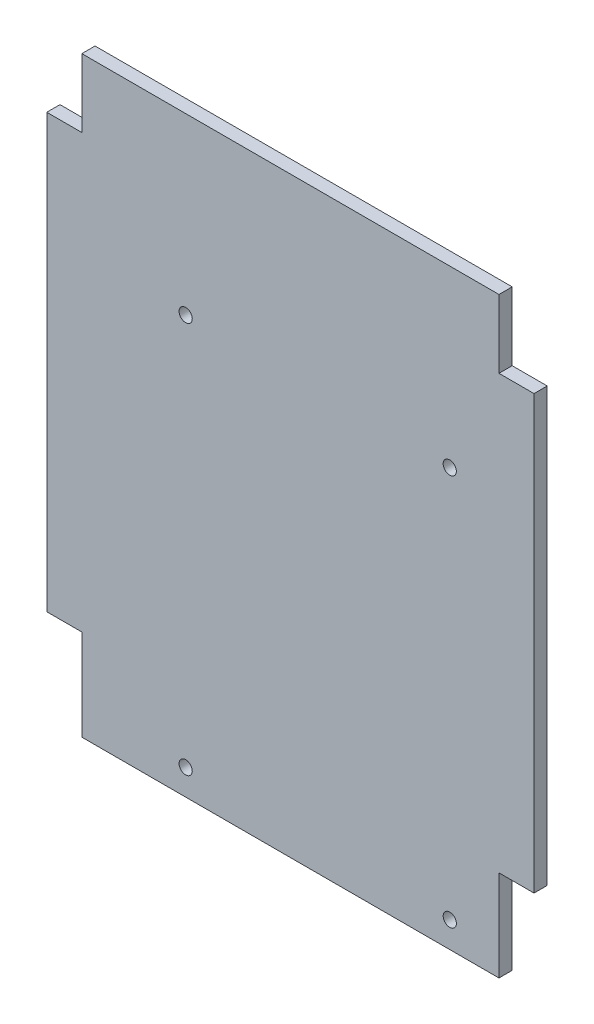
SolidWorks part; units mm, degrees
ref_plane "Front Plane" through (0, 0, 0) normal (0, 0, 1) x (1, 0, 0)
ref_plane "Top Plane" through (0, 0, 0) normal (0, 1, 0) x (1, 0, 0)
ref_plane "Right Plane" through (0, 0, 0) normal (1, 0, 0) x (0, 0, -1)
sketch "Sketch1" plane through (0, 0, 0) normal (0, 0, 1) x (1, 0, 0)
  line L4 (0, -57.4087) -> (0, 73.1354) construction
  line L5 (-53.5, -47.5) -> (-45.8, -47.5)
  line L6 (-53.5, -47.5) -> (-53.5, 47.5)
  line L7 (-53.5, 47.5) -> (-45.8, 47.5)
  line L8 (53.5, -47.5) -> (53.5, 47.5)
  line L9 (-53.5, -47.5) -> (53.5, 47.5) construction
  line L10 (-53.5, 47.5) -> (53.5, -47.5) construction
  line L11 (0, 0) -> (92.3064, 0) construction
  line L12 (-23, -61.8214) -> (35, -61.8214) construction
  line L13 (6, -61.8214) -> (6, -50.4105) construction
  line L24 (45.8039, 47.5) -> (53.5, 47.5)
  line L26 (45.8039, 47.5) -> (45.8039, 62.5)
  line L27 (45.8039, 62.5) -> (-45.8, 62.5)
  line L28 (-45.8, 47.5) -> (-45.8, 62.5)
  line L31 (-45.8, -47.5) -> (-45.8, -67.5)
  line L32 (-45.8, -67.5) -> (45.8, -67.5)
  line L33 (45.8, -67.5) -> (45.8, -47.5)
  line L34 (45.8, -47.5) -> (53.5, -47.5)
  circle A0 centre (35, -61.8214) radius 1.45
  circle A1 centre (35, 24.1786) radius 1.45
  circle A2 centre (-23, -61.8214) radius 1.45
  circle A3 centre (-23, 24.1786) radius 1.45
  point P0 (0, 0)
  point P7 (-33, -61.5907)
  point P8 (-33, -61.8214)
  dimension "D3" = 6
  dimension "D10" = 2.9
  dimension "D11" = 2.9
  dimension "D13" = 2.9
  dimension "D14" = 2.9
  dimension "D1" = 107
  dimension "D2" = 95
  dimension "D9" = 86
  dimension "D12" = 58
  dimension "D15" = 58
  dimension "D17" = 15
  dimension "D18" = 7.7
  dimension "D19" = 7.6961
  dimension "D20" = 7.7
  dimension "D21" = 7.7
  dimension "D22" = 20
extrude "Boss-Extrude2" add sketch "Sketch1" along normal blind 2.9
